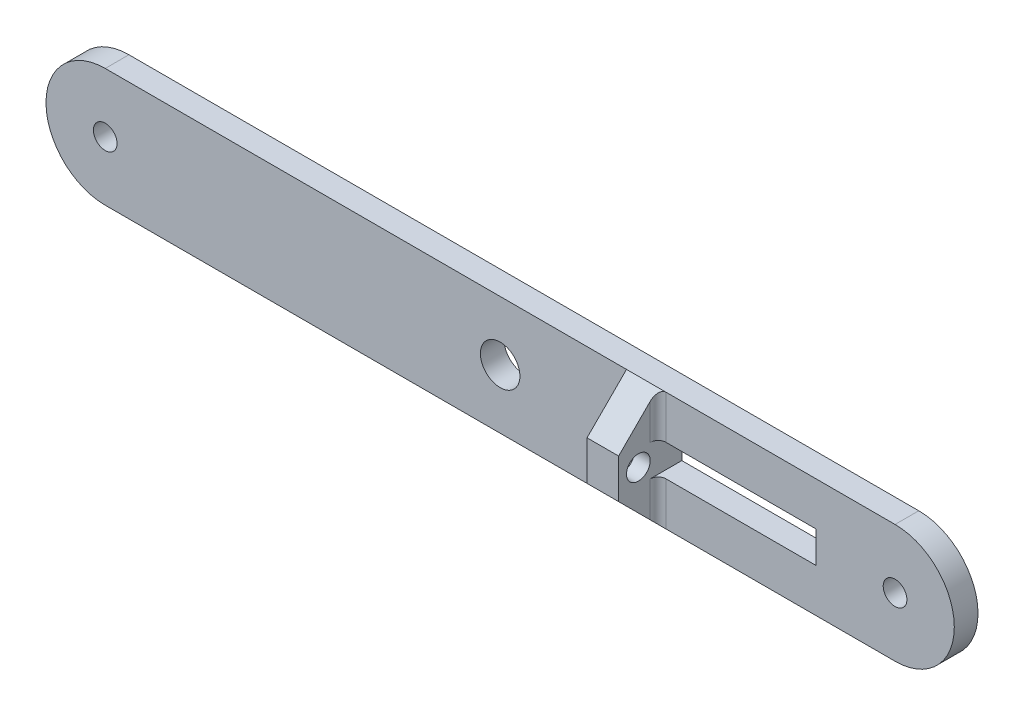
SolidWorks part; units mm, degrees
ref_plane "Plan de face" through (0, 0, 0) normal (0, 0, 1) x (1, 0, 0)
ref_plane "Plan de dessus" through (0, 0, 0) normal (0, 1, 0) x (1, 0, 0)
ref_plane "Plan de droite" through (0, 0, 0) normal (1, 0, 0) x (0, 0, -1)
sketch "Esquisse1" plane through (0, 0, 0) normal (0, 0, 1) x (1, 0, 0)
  line L0 (-74.3787, 0) -> (69.7437, 0) construction
  line L1 (0, 0) -> (0, 19.0596) construction
  line L2 (100, -15) -> (-100, -15)
  line L3 (100, 15) -> (-100, 15)
  line L5 (40, -4) -> (80, -4)
  line L6 (40, -4) -> (40, 4)
  line L7 (40, 4) -> (80, 4)
  line L8 (80, -4) -> (80, 4)
  line L9 (40, -4) -> (80, 4) construction
  line L10 (40, 4) -> (80, -4) construction
  arc A0 (100, -15) -> (100, 15) centre (100, 0) ccw
  circle A1 centre (100, 0) radius 3
  circle A2 centre (-100, 0) radius 3
  arc A3 (-100, -15) -> (-100, 15) centre (-100, 0) cw
  circle A4 centre (0, 0) radius 5
  point P4 (60, 0)
  point P17 (0, -15)
  point P20 (0, 15)
  dimension "D1" = 30
  dimension "D3" = 6
  dimension "D7" = 10
  dimension "D2" = 100
  dimension "D4" = 8
  dimension "D5" = 40
  dimension "D6" = 60
extrude "Boss.-Extru.1" add sketch "Esquisse1" along normal blind 6
sketch "Esquisse2" plane through (40, 0, 0) normal (1, 0, 0) x (0, 0, -1)
  line L0 (0, -4) -> (-6, 4) construction
  line L1 (-6, 4) -> (-6, 0) construction
  line L2 (-6, 4) -> (-6, -4) construction
  line L3 (-6, 0) -> (-15.5036, 0) construction
  line L4 (-6, 15) -> (-6, -15) construction
  line L6 (-16, 5) -> (-16, -5)
  line L8 (-6, 5) -> (-6, -5)
  line L9 (-16, 5) -> (-6, -5) construction
  line L10 (-16, -5) -> (-6, 5) construction
  line L11 (-6, -15) -> (-16, -5)
  line L12 (-6, -15) -> (-6, -5)
  line L13 (-6, 5) -> (-6, 15)
  line L14 (-6, 15) -> (-16, 5)
  circle A0 centre (-11, 0) radius 3
  point P7 (-11, 0)
  dimension "D3" = 6
  dimension "D1" = 10
  dimension "D2" = 10
extrude "Boss.-Extru.2" add sketch "Esquisse2" against normal blind 8
fillet "Congé2" radius 2 2 edges
sketch "Esquisse3" plane through (32, 0, 0) normal (-1, 0, 0) x (0, 0, 1)
  line L0 (11, 0) -> (11, 4) construction
  line L1 (11, 0) -> (14.4641, 2) construction
  line L2 (11, 0) -> (14.4641, -2) construction
  line L3 (11, 4) -> (14.4641, 2)
  line L4 (14.4641, 2) -> (14.4641, -2)
  line L5 (14.4641, -2) -> (11, -4)
  line L6 (7.5359, 2) -> (7.5359, -2)
  line L7 (11, 4) -> (7.5359, 2)
  line L8 (7.5359, -2) -> (11, -4)
  dimension "D2" = 60
  dimension "D3" = 60
extrude "Enlèv. mat.-Extru.1" cut sketch "Esquisse3" against normal blind 4
